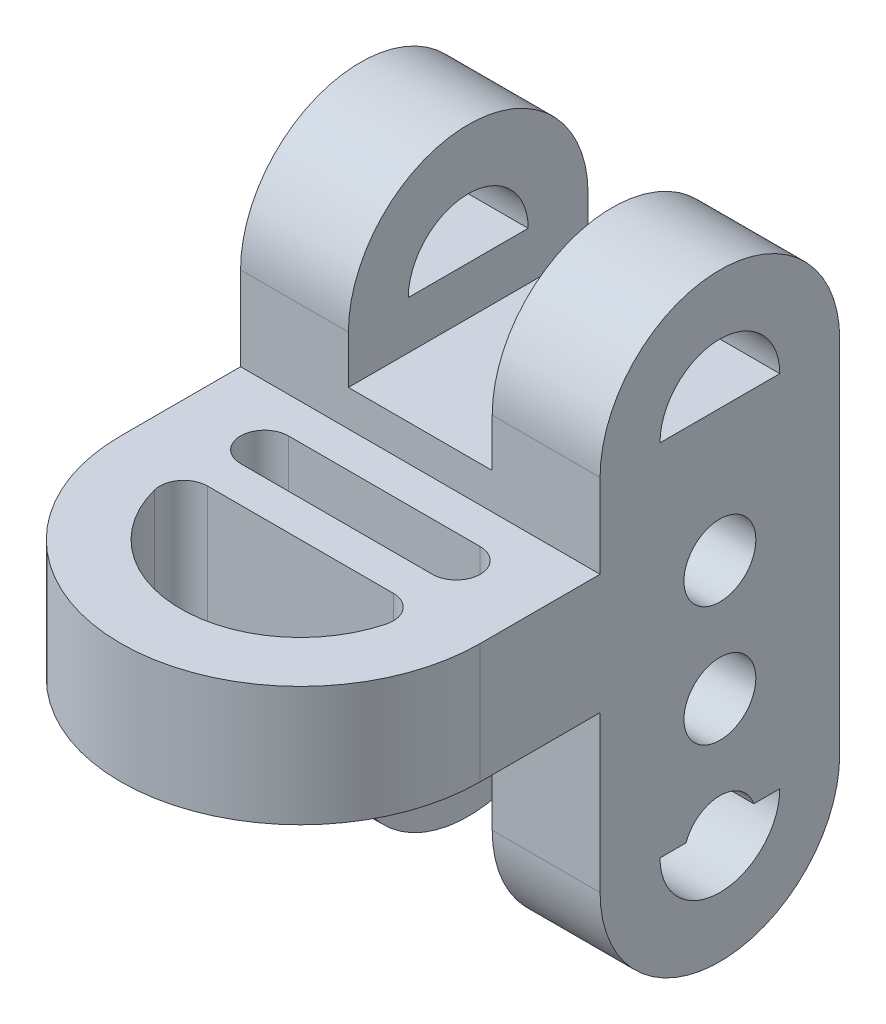
SolidWorks part; units mm, degrees
ref_plane "前视基准面" through (0, 0, 0) normal (0, 0, 1) x (1, 0, 0)
ref_plane "上视基准面" through (0, 0, 0) normal (0, 1, 0) x (1, 0, 0)
ref_plane "右视基准面" through (0, 0, 0) normal (1, 0, 0) x (0, 0, -1)
other "Configuration Table"
sketch "Sketch2" plane through (0, 0, 0) normal (1, 0, 0) x (0, 0, -1)
  line L1 (-5, -7) -> (5, -7)
  line L2 (-5, -7) -> (-5, 8)
  line L4 (5, -7) -> (5, 8)
  line L5 (-5, -7) -> (2.7154, 3.8016) construction
  line L6 (-2.7154, 3.8016) -> (5, -7) construction
  circle A0 centre (0, 8) radius 5
  circle A1 centre (0, 8) radius 2.5
  point P0 (0, 0)
  dimension "D1" = 10
  dimension "D2" = 5
  dimension "D3" = 15
  dimension "D4" = 8
  dimension "8" = 10
extrude "Boss-Extrude2" add sketch "Sketch2" along normal mid plane 15 contours A0 A1 | A0 L2 L1 L4 region at (0, -1.4073, 0) region at (0, 12.8586, 0)
sketch "Sketch3" plane through (0, 0, 0) normal (0, 0, 1) x (1, 0, 0)
  line L0 (0, 13) -> (0, 8) construction
  line L1 (7.5, 13) -> (-7.5, 13) construction
  line L2 (7.5, 8) -> (-7.5, 8) construction
  line L3 (-3, 13) -> (3, 13)
  line L4 (3, 13) -> (3, 3)
  line L5 (3, 3) -> (-3, 3)
  line L6 (-3, 13) -> (-3, 3)
  dimension "D1" = 3
  dimension "D2" = 10
extrude "Cut-Extrude1" cut sketch "Sketch3" against normal mid plane 15
ref_plane "Plane1" through (0, 0.5, 0) normal (0, -1, 0) x (-1, 0, 0)
mirror "Mirror1" about plane through (0, 0.5, 0) normal (0, -1, 0) of "Cut-Extrude1", "Boss-Extrude2"
sketch "Sketch4" plane through (7.5, 0, 0) normal (1, 0, 0) x (0, 0, -1)
  line L0 (0, 0) -> (0, 2.5) construction
  circle A0 centre (0, 2.5) radius 1.5
  circle A1 centre (0, -2.5) radius 1.5
  circle A2 centre (0, -7.5) radius 1.5
  dimension "D1" = 3
  dimension "D2" = 2.5
  dimension "D3" = 3
extrude "Cut-Extrude2" cut sketch "Sketch4" against normal blind 15
sketch "Sketch6" plane through (0, 0, 5) normal (0, 0, 1) x (1, 0, 0)
  line L1 (-3, 8) -> (3, 8)
  line L2 (-3, 8) -> (-3, 6)
  line L3 (-3, 6) -> (3, 6)
  line L4 (3, 8) -> (3, 6)
  dimension "D1" = 6
  dimension "D2" = 2
extrude "Cut-Extrude3" cut sketch "Sketch6" against normal blind 15
sketch "Sketch7" plane through (0, 0, 5) normal (0, 0, 1) x (1, 0, 0)
  line L0 (0, 6) -> (0, -2) construction
  line L1 (-3, 6) -> (3, 6) construction
  line L2 (-3, -2) -> (3, -2) construction
  line L3 (0, -2) -> (0, 2) construction
  line L4 (7.5, -7) -> (7.5, 8) construction
  line L5 (-7.5, -0.5) -> (7.5, -0.5)
  line L6 (-7.5, -0.5) -> (-7.5, 4.5)
  line L7 (-7.5, 4.5) -> (7.5, 4.5)
  line L8 (7.5, -0.5) -> (7.5, 4.5)
  line L9 (-7.5, -0.5) -> (7.5, 4.5) construction
  line L10 (-7.5, 4.5) -> (7.5, -0.5) construction
  dimension "D1" = 5
extrude "Boss-Extrude3" add sketch "Sketch7" along normal blind 5
sketch "Sketch8" plane through (0, 4.5, 0) normal (0, 1, 0) x (1, 0, 0)
  line L0 (0, -10) -> (0, -17.5) construction
  line L1 (7.5, -10) -> (-7.5, -10) construction
  line L2 (-7.5, -10) -> (7.5, -10)
  arc A0 (-7.5, -10) -> (7.5, -10) centre (0, -10) ccw
  arc A1 (-5, -10) -> (5, -10) centre (0, -10) ccw
  line M4 (-7.5, -10) -> (7.5, -10)
  dimension "D2" = 10
  dimension "D1" = 7.5
extrude "Boss-Extrude4" add sketch "Sketch8" against normal blind 5 contours A1 L0 A0 M4 | L0 A1 A0 M4 region at (4.0319, 4.5, 14.0319) region at (-4.0319, 4.5, 14.0319)
fillet "Fillet1" radius 1 2 edges at (-5, 2, 10) (5, 2, 10)
sketch "Sketch9" plane through (0, 4.5, 0) normal (0, 1, 0) x (1, 0, 0)
  line L0 (0, -5) -> (0, -10) construction
  line L3 (7.5, -5) -> (-7.5, -5) construction
  line L4 (3.873, -10) -> (-3.873, -10) construction
  line L9 (0, -10) -> (0, -7.5) construction
  line L10 (0, -7.5) -> (-4, -7.5) construction
  line L11 (-4, -7.5) -> (4, -7.5) construction
  line L12 (-4, -6.5) -> (4, -6.5)
  line L13 (-4, -8.5) -> (4, -8.5)
  arc A0 (-4, -6.5) -> (-4, -8.5) centre (-4, -7.5) ccw
  arc A1 (4, -8.5) -> (4, -6.5) centre (4, -7.5) ccw
  point P9 (0, -7.5)
  dimension "D3" = 1
  dimension "D1" = 4
  dimension "D2" = 8
extrude "Cut-Extrude4" cut sketch "Sketch9" against normal blind 5
